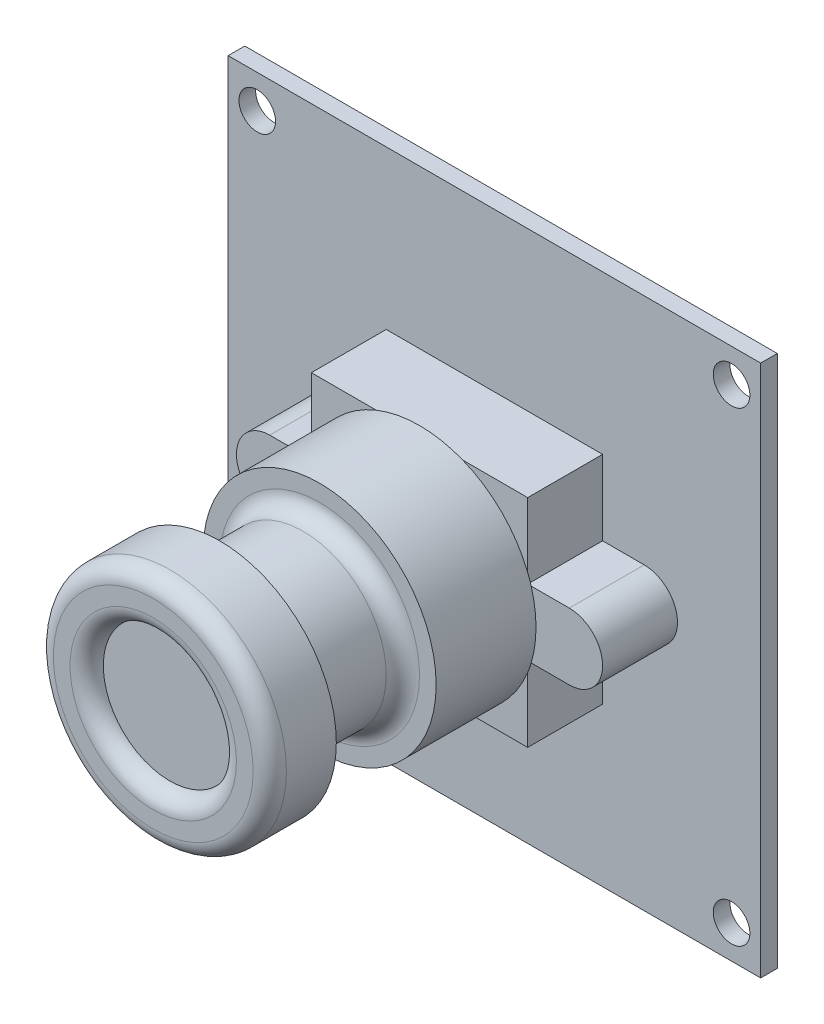
SolidWorks part; units mm, degrees
ref_plane "前视基准面" through (0, 0, 0) normal (0, 0, 1) x (1, 0, 0)
ref_plane "上视基准面" through (0, 0, 0) normal (0, 1, 0) x (1, 0, 0)
ref_plane "右视基准面" through (0, 0, 0) normal (1, 0, 0) x (0, 0, -1)
sketch "草图2" plane through (0, 0, 0) normal (0, 0, 1) x (1, 0, 0)
  line L0 (0, -55) -> (0, 55) construction
  line L1 (-16, -16) -> (16, -16)
  line L2 (-16, -16) -> (-16, 16)
  line L3 (-16, 16) -> (16, 16)
  line L4 (16, -16) -> (16, 16)
  line L5 (-16, -16) -> (16, 16) construction
  line L6 (-16, 16) -> (16, -16) construction
  circle A0 centre (-14.25, -14) radius 1.1
  circle A1 centre (-14.25, 14) radius 1.1
  circle A2 centre (14.25, 14) radius 1.1
  circle A3 centre (14.25, -14) radius 1.1
  point P0 (0, 0)
  dimension "D3" = 2.2
  dimension "D4" = 2.2
  dimension "D6" = 2
  dimension "D7" = 28.5
  dimension "D1" = 32
  dimension "D2" = 32
  dimension "D5" = 28
extrude "凸台-拉伸1" add sketch "草图2" along normal blind 1
sketch "草图3" plane through (0, 0, 1) normal (0, 0, 1) x (1, 0, 0)
  line L1 (-6.5, -6.5) -> (6.5, -6.5)
  line L2 (-6.5, -6.5) -> (-6.5, -2)
  line L3 (-6.5, 6.5) -> (6.5, 6.5)
  line L4 (6.5, -6.5) -> (6.5, -2)
  line L5 (-6.5, -6.5) -> (6.5, 6.5) construction
  line L6 (-6.5, 6.5) -> (6.5, -6.5) construction
  line L7 (-9, 2) -> (-6.5, 2)
  line L8 (-9, -2) -> (-6.5, -2)
  line L9 (-6.5, 2) -> (-6.5, 6.5)
  line L10 (0, -55) -> (0, 55) construction
  line L11 (9, 2) -> (6.5, 2)
  line L12 (9, -2) -> (6.5, -2)
  line L13 (6.5, 2) -> (6.5, 6.5)
  line L14 (0, 16) -> (0, -16) construction
  line L15 (16, 16) -> (-16, 16) construction
  line L16 (-16, -16) -> (16, -16) construction
  arc A0 (-9, 2) -> (-9, -2) centre (-9, 0) ccw
  arc A1 (9, 2) -> (9, -2) centre (9, 0) cw
  point P24 (0, 0)
  dimension "D4" = 4
  dimension "D1" = 13
  dimension "D2" = 13
  dimension "D5" = 18
extrude "凸台-拉伸2" add sketch "草图3" along normal blind 4.5
sketch "草图4" plane through (0, 0, 5.5) normal (0, 0, 1) x (1, 0, 0)
  circle A0 centre (0, 0) radius 7
  dimension "D1" = 14
extrude "凸台-拉伸3" add sketch "草图4" along normal blind 6
sketch "草图5" plane through (0, 0, 11.5) normal (0, 0, 1) x (1, 0, 0)
  circle A0 centre (0, 0) radius 5
  dimension "D1" = 10
extrude "凸台-拉伸4" add sketch "草图5" along normal blind 6
sketch "草图6" plane through (0, 0, 17.5) normal (0, 0, 1) x (1, 0, 0)
  circle A0 centre (0, 0) radius 7 construction
  circle A1 centre (0, 0) radius 7
extrude "凸台-拉伸5" add sketch "草图6" along normal blind 4
sketch "草图9" plane through (0, 0, 21.5) normal (0, 0, 1) x (1, 0, 0)
  circle A0 centre (0, 0) radius 4
  dimension "D1" = 8
extrude "切除-拉伸2" cut sketch "草图9" against normal blind 1
fillet "圆角2" radius 1 4 edges at (5, 0, 11.5) (5, 0, 17.5) (7, 0, 21.5) (4, 0, 21.5)
